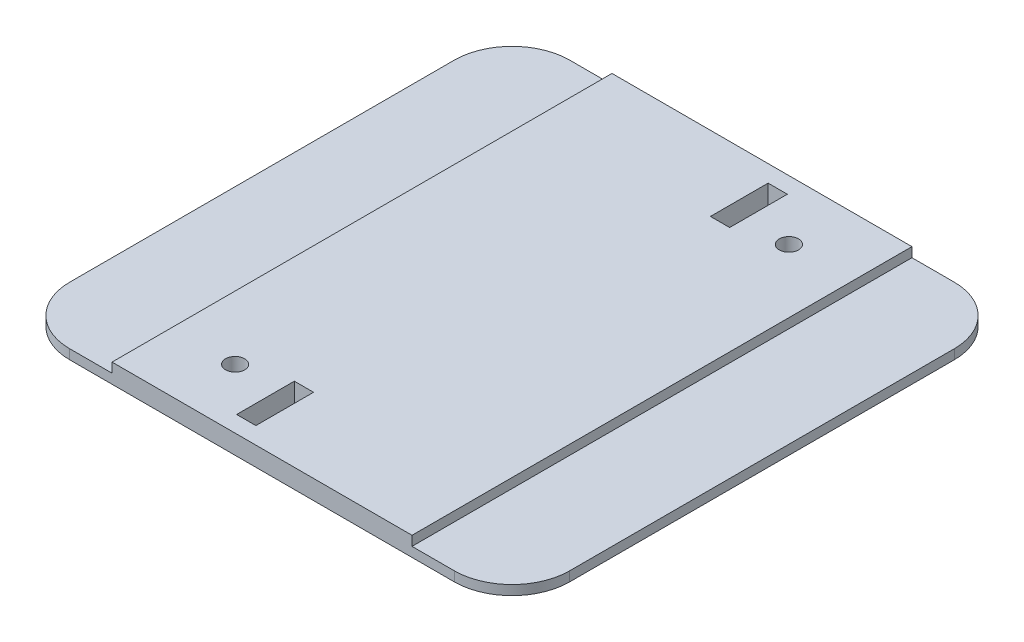
SolidWorks part; units mm, degrees
ref_plane "Front Plane" through (0, 0, 0) normal (0, 0, 1) x (1, 0, 0)
ref_plane "Top Plane" through (0, 0, 0) normal (0, 1, 0) x (1, 0, 0)
ref_plane "Right Plane" through (0, 0, 0) normal (1, 0, 0) x (0, 0, -1)
sketch "Sketch1" plane through (0, 0, 0) normal (0, 1, 0) x (1, 0, 0)
  line L0 (0, 34.664) -> (0, -51.0735) construction
  line L1 (-39, 65) -> (39, 65)
  line L2 (-39, 65) -> (-39, -65)
  line L3 (-39, -65) -> (39, -65)
  line L4 (39, 65) -> (39, -65)
  line L5 (-69.2084, 0) -> (81.5089, 0) construction
  dimension "D1" = 78
  dimension "D2" = 130
extrude "Boss-Extrude1" add sketch "Sketch1" along normal blind 2.5
sketch "Sketch4" plane through (0, 0, 0) normal (0, -1, 0) x (-1, 0, 0)
  line L0 (39, -65) -> (-39, -65) construction
  line L1 (65, 65) -> (-65, 65)
  line L2 (65, 65) -> (65, -65)
  line L3 (65, -65) -> (-65, -65)
  line L4 (-65, 65) -> (-65, -65)
  line L5 (-39, 65) -> (39, 65) construction
  line L6 (0, 118.1215) -> (0, -128.1726) construction
  dimension "D1" = 130
extrude "Boss-Extrude2" add sketch "Sketch4" along normal blind 2.5
sketch "Sketch2" plane through (0, 2.5, 0) normal (0, 1, 0) x (1, 0, 0)
  line L0 (39, 65) -> (-39, 65) construction
  line L2 (39, -65) -> (39, 65) construction
  line L3 (-39, -65) -> (39, -65) construction
  line L5 (-39, 65) -> (-39, -65) construction
  circle A0 centre (22.5, 49.5) radius 2.5
  circle A1 centre (-22.5, -49.5) radius 2.5
  dimension "D3" = 5
  dimension "D4" = 5
  dimension "D1" = 15.5
  dimension "D2" = 16.5
  dimension "D5" = 16.5
  dimension "D6" = 15.5
extrude "Cut-Extrude1" cut sketch "Sketch2" against normal blind 10
sketch "Sketch3" plane through (0, 2.5, 0) normal (0, 1, 0) x (1, 0, 0)
  line L1 (6, 60.6) -> (11, 60.6)
  line L2 (6, 60.6) -> (6, 45.6)
  line L3 (6, 45.6) -> (11, 45.6)
  line L4 (11, 60.6) -> (11, 45.6)
  line L5 (-11, -45.6) -> (-6, -45.6)
  line L6 (-11, -45.6) -> (-11, -60.6)
  line L7 (-11, -60.6) -> (-6, -60.6)
  line L8 (-6, -45.6) -> (-6, -60.6)
  line L9 (-39, -65) -> (39, -65) construction
  line L10 (-39, 65) -> (-39, -65) construction
  line L11 (39, -65) -> (39, 65) construction
  line L12 (39, 65) -> (-39, 65) construction
  dimension "D1" = 5
  dimension "D2" = 5
  dimension "D3" = 15
  dimension "D4" = 4.4
  dimension "D5" = 28
  dimension "D6" = 28
  dimension "D7" = 15
  dimension "D8" = 4.4
extrude "Cut-Extrude2" cut sketch "Sketch3" against normal up to next
fillet "Fillet1" radius 15 4 edges at (-65, -1.25, -65) (65, -1.25, -65) (65, -1.25, 65) (-65, -1.25, 65)
